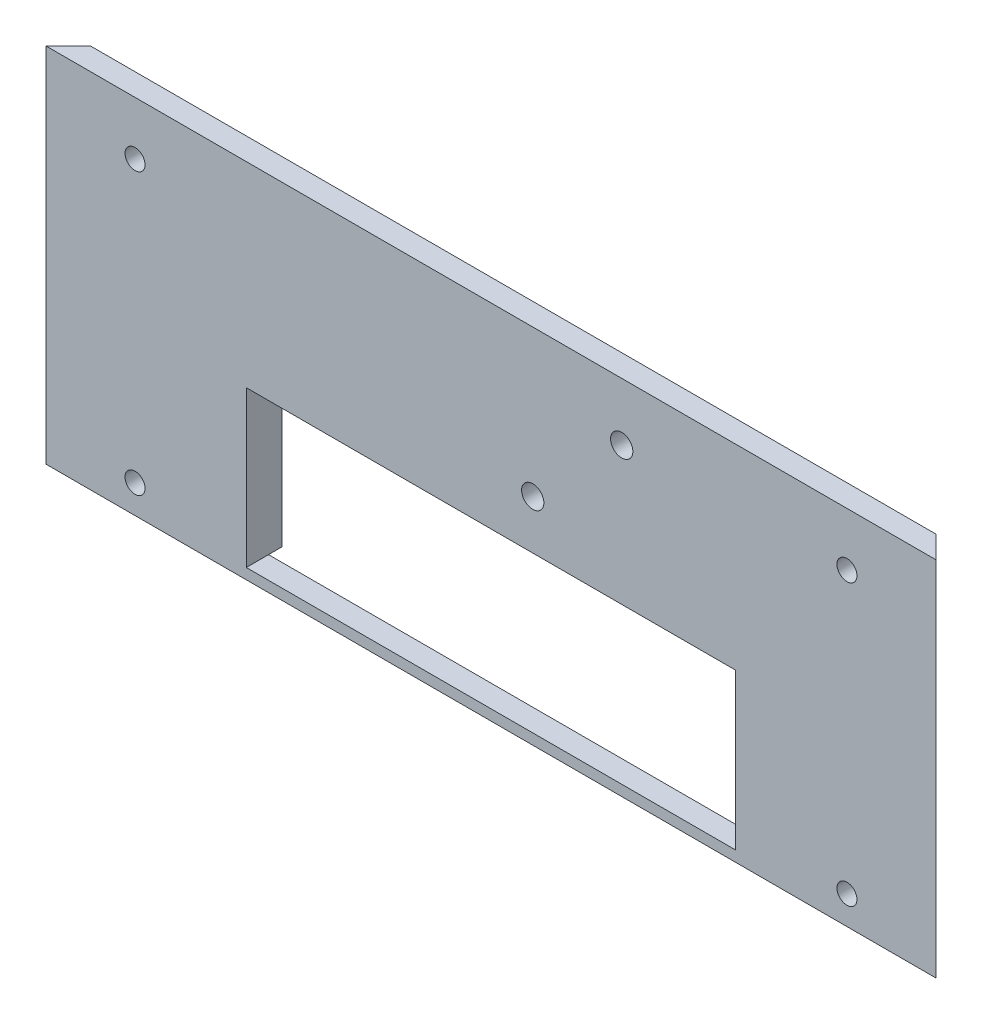
SolidWorks part; units mm, degrees
ref_plane "Front Plane" through (0, 0, 0) normal (0, 0, 1) x (1, 0, 0)
ref_plane "Top Plane" through (0, 0, 0) normal (0, 1, 0) x (1, 0, 0)
ref_plane "Right Plane" through (0, 0, 0) normal (1, 0, 0) x (0, 0, -1)
sketch "Sketch1" plane through (0, 0, 0) normal (0, 0, 1) x (1, 0, 0)
  line L0 (100, 84) -> (100, -37.3998) construction
  line L1 (0, 0) -> (200, 0)
  line L2 (0, 0) -> (0, 84)
  line L3 (0, 84) -> (200, 84)
  line L4 (200, 0) -> (200, 84)
  line L5 (0, 42) -> (200, 42) construction
  circle A0 centre (20, 9) radius 2.25
  circle A1 centre (180, 9) radius 2.25
  circle A4 centre (20, 72) radius 2.25
  circle A5 centre (180, 72) radius 2.25
  circle A6 centre (109.3775, 51) radius 2.5
  circle A7 centre (129.3775, 71) radius 2.5
  dimension "D3" = 20
  dimension "D5" = 4.5
  dimension "D8" = 20
  dimension "D1" = 84
  dimension "D2" = 200
  dimension "D4" = 9
  dimension "D6" = 2
  dimension "D7" = 12
  dimension "D9" = 20
  dimension "D10" = 33
extrude "Boss-Extrude1" add sketch "Sketch1" against normal blind 5
sketch "Sketch2" plane through (0, 0, -5) normal (0, 0, -1) x (-1, 0, 0)
  line L0 (0, 0) -> (-200, 0) construction
  line L1 (0, 0) -> (-200, 0) construction
  line L2 (0, 5) -> (-200, 5)
  line L3 (-200, 5) -> (-200, 84)
  line L4 (-200, 84) -> (0, 84)
  line L5 (0, 84) -> (0, 5)
  circle A1 centre (-20, 9) radius 2.25 construction
  circle A2 centre (-180, 9) radius 2.25 construction
  circle A5 centre (-20, 9) radius 2.25
  circle A6 centre (-180, 9) radius 2.25
  circle A8 centre (-20, 72) radius 2.25 construction
  circle A9 centre (-180, 72) radius 2.25 construction
  circle A10 centre (-20, 72) radius 2.25
  circle A11 centre (-180, 72) radius 2.25
  dimension "D1" = 5
extrude "Boss-Extrude2" add sketch "Sketch2" along normal blind 3
chamfer "Chamfer1" distance 8 angle 45 3 edges at (200, 44.5, -8) (0, 44.5, -8) (100, 84, -8)
chamfer "Chamfer3" distance 3 angle 45 1 edges at (100, 84, -8)
sketch "Sketch3" plane through (100, 0, -100) normal (0.7071, 0, -0.7071) x (-0.7071, 0, -0.7071)
  line L0 (-141.4214, 0) -> (-141.4214, 2.6)
  line L1 (-141.4214, 0) -> (-141.4214, 84) construction
  line L2 (-141.4214, 2.6) -> (-134.3503, 2.6)
  line L4 (-134.3503, 2.6) -> (-134.3503, 0)
  line L5 (-134.3503, 0) -> (-141.4214, 0)
  line L6 (-130.1076, 5) -> (-134.3503, 5) construction
  dimension "D1" = 2.4
extrude "Cut-Extrude1" cut sketch "Sketch3" along direction (1, 0, 0) on the side against the normal through all
sketch "Sketch4" plane through (0, 0, 0) normal (0, 0, 1) x (1, 0, 0)
  circle A0 centre (109.3775, 51) radius 2.5 construction
  circle A1 centre (129.3775, 71) radius 2.5
  circle A2 centre (129.3775, 71) radius 2.5
  circle A3 centre (109.3775, 51) radius 2.5
  dimension "D1" = 0
extrude "Cut-Extrude2" cut sketch "Sketch4" against normal through all
sketch "Sketch6" plane through (0, 0, -8) normal (0, 0, -1) x (-1, 0, 0)
  line L0 (-192, 5) -> (-8, 5) construction
  line L1 (-45, 5) -> (-155, 5)
  line L2 (-45, 5) -> (-45, 40)
  line L3 (-45, 40) -> (-155, 40)
  line L4 (-155, 5) -> (-155, 40)
  line L5 (-100, 81) -> (-100, 5) construction
  line L6 (-8, 81) -> (-192, 81) construction
  dimension "D1" = 110
  dimension "D2" = 35
extrude "Cut-Extrude3" cut sketch "Sketch6" against normal through all both and the other way through all
